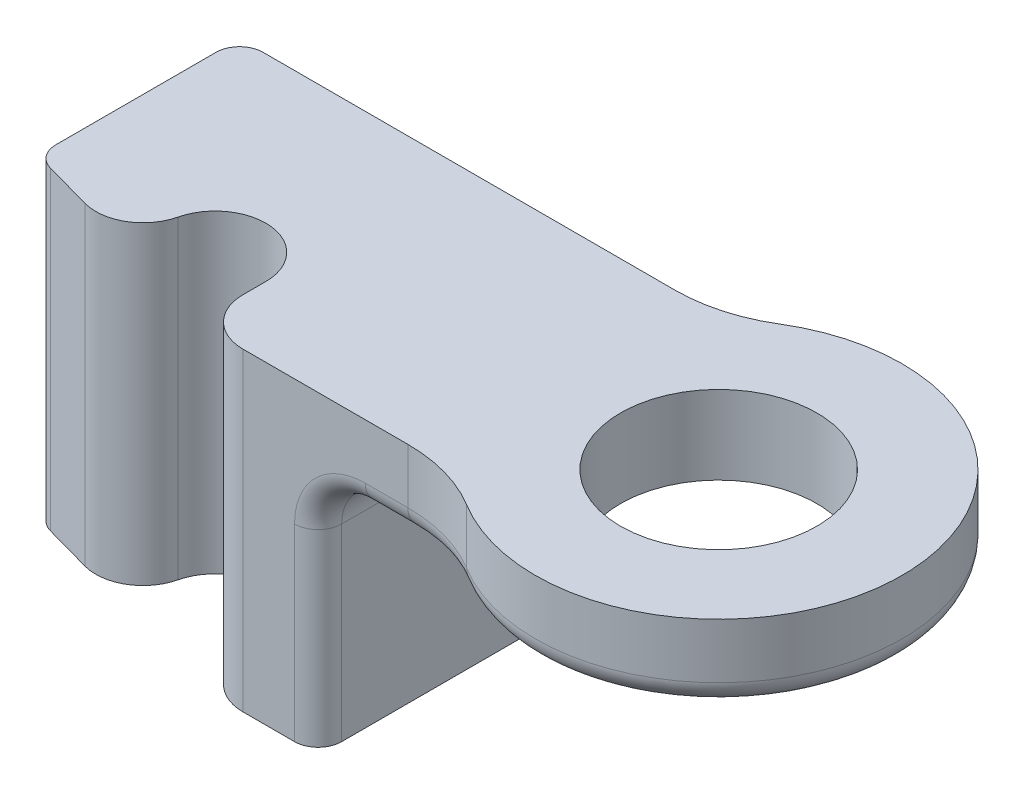
SolidWorks part; units mm, degrees
ref_plane "Front Plane" through (0, 0, 0) normal (0, 0, 1) x (1, 0, 0)
ref_plane "Top Plane" through (0, 0, 0) normal (0, 1, 0) x (1, 0, 0)
ref_plane "Right Plane" through (0, 0, 0) normal (1, 0, 0) x (0, 0, -1)
sketch "Sketch1" plane through (0, 0, 0) normal (0, 1, 0) x (1, 0, 0)
  line L0 (0, 0) -> (7, 0)
  line L1 (0, 3.75) -> (7, 3.75)
  line L2 (0, -3.75) -> (7, -3.75)
  circle A0 centre (0, 0) radius 3.75
  circle A1 centre (7, 0) radius 3.75
  dimension "D1" = 7.5
  dimension "D2" = 7
extrude "Boss-Extrude2" add sketch "Sketch1" along normal blind 30 contours A1 A0 | A1 A0 | A1 A0 L2 | A1 L1 A0 | L0 A1 A0 | A0 A1 L0 region at (3.5, 0, -0.5072) region at (-0.0731, 0, 0) region at (3.5, 0, 0.5072) region at (7.0731, 0, 0) region at (3.5, 0, -3.0985) region at (3.5, 0, 3.0985)
sketch "Sketch4" plane through (0, 30, 0) normal (0, 1, 0) x (1, 0, 0)
  line L2 (7, 3.75) -> (0, 3.75)
  line L3 (0, -3.75) -> (7, -3.75)
  line L4 (7, 3.75) -> (0, 3.75)
  line L5 (0, -3.75) -> (7, -3.75)
  circle A0 centre (7, 0) radius 3.75
  arc A3 (0, 3.75) -> (0, -3.75) centre (0, 0) ccw
  arc A4 (7, -3.75) -> (7, 3.75) centre (7, 0) ccw
  arc A5 (0, 3.75) -> (0, -3.75) centre (0, 0) ccw
  arc A6 (7, -3.75) -> (7, 3.75) centre (7, 0) ccw
  line M6 (7, 3.75) -> (0, 3.75)
  arc M7 (0, 3.75) -> (0, -3.75) centre (0, 0) ccw
  line M8 (0, -3.75) -> (7, -3.75)
  dimension "D1" = 0
extrude "Cut-Extrude3" cut sketch "Sketch4" against normal blind 13 contours A0 M6 M7 M8 region at (0.5548, 30, 0)
sketch "Sketch5" plane through (0, 0, 0) normal (0, -1, 0) x (1, 0, 0)
  line L0 (10.75, 0) -> (10.75, -52.5)
  line L1 (10.75, -52.5) -> (-39.25, -38.6338)
  line L2 (-39.25, -38.6338) -> (-39.25, -35)
  line L3 (-39.25, -35) -> (-9.25, -35)
  line L4 (-9.25, -35) -> (-9.25, 35)
  line L5 (-9.25, 35) -> (-39.25, 35)
  line L6 (-39.25, 35) -> (-39.25, 38.6338)
  line L7 (-39.25, 38.6338) -> (10.75, 52.5)
  line L8 (10.75, 52.5) -> (10.75, 0)
  arc A0 (7, -3.75) -> (7, 3.75) centre (7, 0) ccw construction
  dimension "D1" = 50
  dimension "D2" = 105
  dimension "D3" = 74.5
  dimension "D4" = 70
  dimension "D5" = 30
extrude "Boss-Extrude3" add sketch "Sketch5" against normal blind 3
sketch "Sketch6" plane through (0, 3, 0) normal (0, 1, 0) x (1, 0, 0)
  line L46 (-24.25, -42.7936) -> (-24.25, 42.7936)
  line L54 (10.75, 52.5) -> (-39.25, 38.6338)
  line L55 (10.75, -52.5) -> (10.75, 52.5)
  line L56 (-39.25, -38.6338) -> (10.75, -52.5)
  line L57 (-39.25, -35) -> (-39.25, -38.6338)
  line L58 (-9.25, -35) -> (-39.25, -35)
  line L59 (-9.25, 35) -> (-9.25, -35)
  line L60 (-39.25, 35) -> (-9.25, 35)
  line L61 (-39.25, 38.6338) -> (-39.25, 35)
  line L62 (10.75, 52.5) -> (-39.25, 38.6338)
  line L63 (10.75, -52.5) -> (10.75, 52.5)
  line L64 (-39.25, -38.6338) -> (10.75, -52.5)
  line L65 (-39.25, -35) -> (-39.25, -38.6338)
  line L66 (-9.25, -35) -> (-39.25, -35)
  line L67 (-9.25, 35) -> (-9.25, -35)
  line L68 (-39.25, 35) -> (-9.25, 35)
  line L69 (-39.25, 38.6338) -> (-39.25, 35)
  line M12 (10.75, 52.5) -> (-39.25, 38.6338)
  line M13 (-39.25, 38.6338) -> (-39.25, 35)
  line M14 (-39.25, 35) -> (-9.25, 35)
  line M16 (-9.25, -35) -> (-39.25, -35)
  line M17 (-39.25, -35) -> (-39.25, -38.6338)
  line M18 (-39.25, -38.6338) -> (10.75, -52.5)
  dimension "D2" = 15
  dimension "D1" = 0
extrude "Boss-Extrude4" add sketch "Sketch6" along normal blind 14 contours L46 M18 M16 M17 | L46 M14 M12 M13 region at (-30.8399, 3, 37.983) region at (-30.8399, 3, -37.983)
sketch "Sketch7" plane through (0, 17, 0) normal (0, 1, 0) x (1, 0, 0)
  line L0 (-39.25, 38.6338) -> (-39.25, -38.6338)
  line L1 (-39.25, -38.6338) -> (-24.25, -42.7936)
  line L2 (-24.25, -42.7936) -> (2.25, -42.7936)
  line L3 (2.25, -42.7936) -> (2.25, 42.7936)
  line L4 (2.25, 42.7936) -> (-24.25, 42.7936)
  line L5 (-24.25, 42.7936) -> (-39.25, 38.6338)
  dimension "D1" = 41.5
extrude "Boss-Extrude5" add sketch "Sketch7" along normal blind 3
sketch "Sketch8" plane through (0, 20, 0) normal (0, 1, 0) x (1, 0, 0)
  line L0 (-28.25, 38.3422) -> (-28.25, 35)
  line L3 (-24.25, -42.7936) -> (-24.25, 42.7936)
  line L4 (-28.25, 38.3422) -> (-28.25, 41.6843)
  line L5 (-28.25, -41.6843) -> (-28.25, -38.3422)
  line L6 (-28.25, -38.3422) -> (-28.25, -35)
  line L11 (10.75, 52.5) -> (-39.25, 38.6338)
  line L12 (10.75, -52.5) -> (10.75, 52.5)
  line L13 (-39.25, -38.6338) -> (10.75, -52.5)
  line L14 (-39.25, -35) -> (-39.25, -38.6338)
  line L15 (-9.25, -35) -> (-39.25, -35)
  line L16 (-9.25, 35) -> (-9.25, -35)
  line L17 (-39.25, 35) -> (-9.25, 35)
  line L18 (-39.25, 38.6338) -> (-39.25, 35)
  line L19 (10.75, 52.5) -> (-39.25, 38.6338)
  line L20 (10.75, -52.5) -> (10.75, 52.5)
  line L21 (-39.25, -38.6338) -> (10.75, -52.5)
  line L22 (-39.25, -35) -> (-39.25, -38.6338)
  line L23 (-9.25, -35) -> (-39.25, -35)
  line L24 (-9.25, 35) -> (-9.25, -35)
  line L25 (-39.25, 35) -> (-9.25, 35)
  line L26 (-39.25, 38.6338) -> (-39.25, 35)
  circle A0 centre (-28.25, -38.3422) radius 1.5
  circle A1 centre (-28.25, 38.3422) radius 1.5
  dimension "D1" = 3
  dimension "D3" = 4
  dimension "D2" = 0
extrude "Cut-Extrude4" cut sketch "Sketch8" against normal through all contours A1 | A0
sketch "Sketch3" plane through (0, 0, 0) normal (0, -1, 0) x (1, 0, 0)
  circle A0 centre (0, 0) radius 1.5
  dimension "D1" = 3
extrude "Cut-Extrude2" cut sketch "Sketch3" against normal through all
sketch "Sketch2" plane through (0, 30, 0) normal (0, 1, 0) x (1, 0, 0)
  circle A0 centre (7, 0) radius 1.5
  dimension "D1" = 3
extrude "Cut-Extrude1" cut sketch "Sketch2" against normal blind 30
sketch "Sketch9" plane through (2.25, 0, 0) normal (1, 0, 0) x (0, 0, -1)
  line L0 (3.75, 17) -> (42.7936, 17) construction
  line L1 (4.7936, 34) -> (14.7936, 34)
  line L2 (4.7936, 34) -> (4.7936, 17)
  line L3 (4.7936, 17) -> (14.7936, 17)
  line L4 (14.7936, 34) -> (14.7936, 17)
  line L6 (42.7936, 20) -> (42.7936, 17) construction
  dimension "D1" = 28
  dimension "D2" = 10
  dimension "D3" = 17
extrude "Boss-Extrude6" add sketch "Sketch9" along normal blind 8.5
sketch "Sketch11" plane through (10.75, 0, 0) normal (1, 0, 0) x (0, 0, -1)
  line L0 (43.5, 3) -> (43.5, 4)
  line L1 (51.5, 4) -> (51.5, 3)
  line L5 (-52.5, 0) -> (52.5, 0)
  line L6 (52.5, 0) -> (52.5, 3)
  line L7 (52.5, 3) -> (0, 3)
  line L8 (0, 3) -> (-52.5, 3)
  line L9 (-52.5, 3) -> (-52.5, 0)
  line L10 (-52.5, 0) -> (52.5, 0)
  line L11 (52.5, 0) -> (52.5, 3)
  line L12 (52.5, 3) -> (0, 3)
  line L13 (0, 3) -> (-52.5, 3)
  line L14 (-52.5, 3) -> (-52.5, 0)
  arc A0 (43.5, 4) -> (51.5, 4) centre (47.5, 4) cw
  circle A1 centre (47.5, 4) radius 0.875
  line M8 (52.5, 3) -> (0, 3)
  dimension "D4" = 4
  dimension "D5" = 1.75
  dimension "D2" = 1
  dimension "D3" = 5
  dimension "D1" = 0
extrude "Boss-Extrude7" add sketch "Sketch11" against normal blind 10 contours A0 L0 L1 A1 M8 region at (10.75, 5.2584, -47.5)
sketch "Sketch12" plane through (0, 3, 0) normal (0, -1, 0) x (1, 0, 0)
  line L3 (7.1441, -51.5) -> (0.75, -49.7268)
  line L4 (0.75, -49.7268) -> (0.75, -51.5)
  line L5 (0.75, -51.5) -> (7.1441, -51.5)
  line L6 (7.1441, -51.5) -> (0.75, -49.7268)
  line L7 (0.75, -49.7268) -> (0.75, -51.5)
  line L8 (0.75, -51.5) -> (7.1441, -51.5)
  dimension "D1" = 0
extrude "Cut-Extrude6" cut sketch "Sketch12" against normal blind 10
sketch "Sketch13" plane through (0, 0, -14.7936) normal (0, 0, -1) x (-1, 0, 0)
  line L0 (-7.75, 34) -> (-7.75, 25.5)
  line L1 (-2.25, 20) -> (1.5008, 20)
  line L5 (-2.25, 17) -> (-2.25, 20)
  line L6 (-2.25, 20) -> (-2.25, 34)
  line L7 (-2.25, 34) -> (-10.75, 34)
  line L8 (-10.75, 34) -> (-10.75, 17)
  line L9 (-10.75, 17) -> (-2.25, 17)
  line L10 (-2.25, 17) -> (-2.25, 20)
  line L11 (-2.25, 20) -> (-2.25, 34)
  line L12 (-2.25, 34) -> (-10.75, 34)
  line L13 (-10.75, 34) -> (-10.75, 17)
  line L14 (-10.75, 17) -> (-2.25, 17)
  arc A0 (-7.75, 25.5) -> (-2.25, 20) centre (-2.25, 25.5) ccw
  line M7 (-2.25, 20) -> (-2.25, 34)
  line M8 (-2.25, 34) -> (-10.75, 34)
  dimension "D2" = 3
  dimension "D1" = 0
extrude "Cut-Extrude7" cut sketch "Sketch13" against normal up to next contours L0 A0 M7 M8 region at (4.8599, 27.5314, -14.7936)
sketch "Sketch14" plane through (10.75, 0, 0) normal (1, 0, 0) x (0, 0, -1)
  line L0 (14.7936, 34) -> (4.7936, 34) construction
  line L1 (4.7936, 34) -> (4.7936, 17) construction
  circle A0 centre (9.1236, 29.69) radius 0.875
  dimension "D3" = 1.75
  dimension "D1" = 4.31
  dimension "D2" = 4.33
extrude "Cut-Extrude8" cut sketch "Sketch14" against normal blind 10 contours A0
sketch "Sketch15" plane through (0, 20, 0) normal (0, 1, 0) x (1, 0, 0)
  line L0 (-39.25, -25.7936) -> (-17.25, -25.7936)
  line L1 (-39.25, 38.6338) -> (-39.25, -38.6338) construction
  line L2 (-17.25, -25.7936) -> (-17.25, -42.7936)
  line L4 (-24.25, -42.7936) -> (2.25, -42.7936) construction
  line L13 (-24.25, 42.7936) -> (-39.25, 38.6338)
  line L14 (-39.25, 38.6338) -> (-39.25, -38.6338)
  line L15 (-39.25, -38.6338) -> (-24.25, -42.7936)
  line L16 (-24.25, -42.7936) -> (2.25, -42.7936)
  line L17 (2.25, -42.7936) -> (2.25, 4.7936)
  line L18 (2.25, 4.7936) -> (2.25, 14.7936)
  line L19 (2.25, 14.7936) -> (2.25, 42.7936)
  line L20 (2.25, 42.7936) -> (-24.25, 42.7936)
  line L21 (-24.25, 42.7936) -> (-39.25, 38.6338)
  line L22 (-39.25, 38.6338) -> (-39.25, -38.6338)
  line L23 (-39.25, -38.6338) -> (-24.25, -42.7936)
  line L24 (-24.25, -42.7936) -> (2.25, -42.7936)
  line L25 (2.25, -42.7936) -> (2.25, 4.7936)
  line L26 (2.25, 4.7936) -> (2.25, 14.7936)
  line L27 (2.25, 14.7936) -> (2.25, 42.7936)
  line L28 (2.25, 42.7936) -> (-24.25, 42.7936)
  circle M12 centre (-28.25, -38.3422) radius 1.5
  line M15 (-39.25, 38.6338) -> (-39.25, -38.6338)
  line M16 (-39.25, -38.6338) -> (-24.25, -42.7936)
  line M17 (-24.25, -42.7936) -> (2.25, -42.7936)
  dimension "D1" = 22
  dimension "D2" = 17
  dimension "D3" = 0
extrude "Boss-Extrude8" add sketch "Sketch15" along normal blind 20 contours L2 L0 M15 M16 M17 M12 region at (-27.6924, 20, 33.5474)
sketch "Sketch16" plane through (-17.25, 0, 0) normal (1, 0, 0) x (0, 0, -1)
  line L0 (-25.7936, 40) -> (-25.7936, 20) construction
  line L1 (-42.7936, 40) -> (-25.7936, 40)
  line L2 (-42.7936, 40) -> (-42.7936, 35)
  line L3 (-42.7936, 35) -> (-25.7936, 35)
  line L4 (-25.7936, 40) -> (-25.7936, 35)
  dimension "D1" = 5
extrude "Boss-Extrude9" add sketch "Sketch16" along normal blind 25
sketch "Sketch17" plane through (0, 40, 0) normal (0, 1, 0) x (1, 0, 0)
  line L0 (-0.25, -34.2936) -> (7.75, -34.2936)
  line L1 (7.75, -25.7936) -> (7.75, -42.7936) construction
  circle A0 centre (-0.25, -34.2936) radius 6.25
  dimension "D1" = 12.5
  dimension "D2" = 8
extrude "Cut-Extrude9" cut sketch "Sketch17" against normal up to next contours A0
sketch "Sketch18" plane through (0, 40, 0) normal (0, 1, 0) x (1, 0, 0)
  circle A0 centre (-0.25, -34.2936) radius 11.6726
  circle A1 centre (-0.25, -34.2936) radius 6.25 construction
  circle A2 centre (-0.25, -34.2936) radius 6.25
extrude "Boss-Extrude10" add sketch "Sketch18" against normal up to surface (5 mm away) up to face at (-0.25, 35, 40.5436)
fillet "Fillet1" radius 3 1 edges at (-17.25, 35, 34.2936)
sketch "Sketch19" plane through (0, 20, 0) normal (0, 1, 0) x (1, 0, 0)
  line L1 (2.25, -42.7936) -> (-16.75, -42.7936)
  line L2 (2.25, -42.7936) -> (2.25, -24.7936)
  line L3 (2.25, -24.7936) -> (-16.75, -24.7936)
  line L4 (-16.75, -42.7936) -> (-16.75, -24.7936)
  dimension "D1" = 19
  dimension "D2" = 18
extrude "Cut-Extrude10" cut sketch "Sketch19" against normal up to next
fillet "Fillet2" radius 3 8 edges at (9.6517, 3, 2.6517) (9.6517, 3, -2.6517) (3.5, 3, -3.75) (-3.75, 3, 0) (-24.25, 3, -38.8968) (5.75, 3, -43.5) (-24.25, 3, 38.8968) (3.5, 3, 3.75)
fillet "Fillet3" radius 1.5 7 edges at (2.25, 18.5, 24.7936) (-16.75, 18.5, 24.7936) (-39.25, 30, 25.7936) (-39.25, 20, 38.6338) (-39.25, 10, -38.6338)
sketch "Sketch20" plane through (-12.752, 0, 45.9823) normal (-0.2672, 0, 0.9636) x (0.9636, 0, 0.2672)
  line L0 (-4.7047, 20) -> (31.2156, 20)
  line L1 (31.2156, 20) -> (31.2156, 52.4903)
  line L2 (31.2156, 52.4903) -> (-36.9169, 52.4903)
  line L3 (-36.9169, 52.4903) -> (-36.9169, 20)
  line L4 (-36.9169, 20) -> (-4.7047, 20)
  line L6 (-50.798, 59.4535) -> (43.9815, 59.4535)
  line L7 (-50.798, 59.4535) -> (-50.798, -6.6451)
  line L8 (-11.9319, 17) -> (-4.7047, 17)
  line L9 (-4.7047, 17) -> (-4.7047, 20)
  line L10 (-4.7047, 20) -> (-5.1865, 20)
  line L11 (-5.1865, 20) -> (-5.1865, 32)
  line L12 (-2.2956, 35) -> (3.4862, 35)
  line L13 (3.4862, 35) -> (3.4862, 40)
  line L14 (3.4862, 40) -> (-11.9319, 40)
  line L15 (-11.9319, 40) -> (-11.9319, 17)
  line L16 (-11.9319, 17) -> (-4.7047, 17)
  line L17 (-4.7047, 17) -> (-4.7047, 20)
  line L18 (-4.7047, 20) -> (-5.1865, 20)
  line L19 (-5.1865, 20) -> (-5.1865, 32)
  line L20 (-2.2956, 35) -> (3.4862, 35)
  line L21 (3.4862, 35) -> (3.4862, 40)
  line L22 (3.4862, 40) -> (-11.9319, 40)
  line L23 (-11.9319, 40) -> (-11.9319, 17)
  line L24 (-50.798, -6.6451) -> (43.9815, -6.6451)
  line L25 (43.9815, 59.4535) -> (43.9815, -6.6451)
  ellipse E1 centre (-2.2956, 32) end of major axis (-2.2956, 35) minor radius 2.8909 (-2.2956, 35) -> (-5.1865, 32) ccw
  ellipse E2 centre (-2.2956, 32) end of major axis (-2.2956, 35) minor radius 2.8909 (-2.2956, 35) -> (-5.1865, 32) ccw
  line M11 (-26.3574, 40) -> (-26.3574, 0)
  line M12 (-26.3574, 0) -> (24.389, 0)
  line M13 (24.389, 0) -> (24.389, 3)
  line M14 (24.389, 3) -> (-8.8187, 3)
  ellipse M15 centre (-8.8187, 6) end of major axis (-5.7055, 6) minor radius 3 (-8.8187, 3) -> (-11.9319, 6) cw
  line M16 (-11.9319, 6) -> (-11.9319, 17)
  line M17 (-11.9319, 17) -> (-11.9319, 40)
  dimension "D1" = 0
extrude "Cut-Extrude11" cut sketch "Sketch20" against normal through all contours L25 L6 L7 L24 L17 L16 L4 L3 L2 L1 L0 M16 M15 M14 M13 M12 M11 | L16 L17 L4 M17 | L4 M11 M12 M13 M14 M15 M16 M17 region at (-20.7678, 18.5, 43.7593) region at (-24.493, 7.6497, 42.7262) region at (-16.0363, 58.298, 45.0715)
sketch "Sketch21" plane through (0, 40, 0) normal (0, 1, 0) x (1, 0, 0)
  line L0 (-25.0294, -38.3422) -> (-25.0294, -42.5775)
  line L1 (-38.1509, -38.9386) -> (-24.25, -42.7936) construction
  line L2 (-31.4706, -38.3422) -> (-31.4706, -41.0712)
  line L3 (-31.4706, -41.0712) -> (-25.0294, -42.5775)
  circle A0 centre (-28.25, -38.3422) radius 3.2206
  line M5 (-38.1509, -38.9386) -> (-24.25, -42.7936)
  circle M9 centre (-28.25, -38.3422) radius 1.5
extrude "Cut-Extrude12" cut sketch "Sketch21" against normal through all contours A0 L0 M5 | A0 M9 | A0 L2 M5 region at (-26.3557, 40, 40.8333) region at (-25.982, 40, 41.3248) region at (-30.962, 40, 40.4045)
fillet "Fillet4" radius 3 2 edges at (-25.0294, 30, 42.5775) (-31.4706, 30, 40.7912)
fillet "Fillet5" radius 3 1 edges at (-24.25, 30, 42.7936)
fillet "Fillet6" radius 10 2 edges at (-8.25, 37.5, 25.7936) (-8.25, 37.5, 42.7936)
fillet "Fillet7" radius 1.5 9 edges at (-17.25, 26, 25.7936) (-16.3713, 34.1213, 25.7936) (-12.8947, 35, 25.7936) (-8.834, 35, 25.4207) (11.4226, 35, 34.2936) (-8.834, 35, 43.1666) (-12.8947, 35, 42.7936) (-16.3713, 34.1213, 42.7936) (-17.25, 26, 42.7936)
